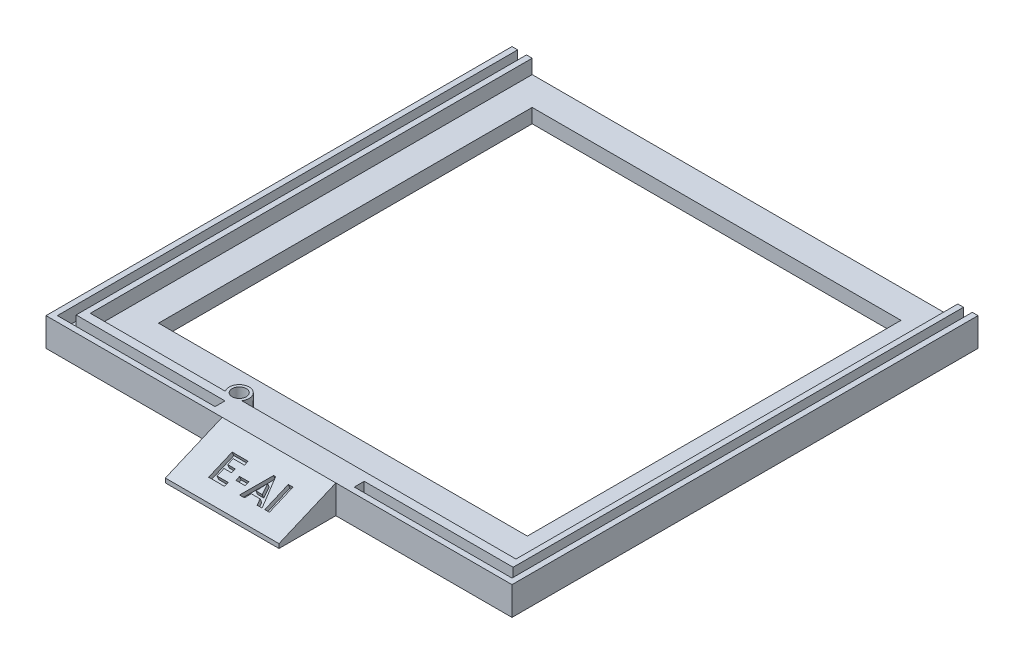
SolidWorks part; units mm, degrees
ref_plane "Front Plane" through (0, 0, 0) normal (0, 0, 1) x (1, 0, 0)
ref_plane "Top Plane" through (0, 0, 0) normal (0, 1, 0) x (1, 0, 0)
ref_plane "Right Plane" through (0, 0, 0) normal (1, 0, 0) x (0, 0, -1)
sketch "Sketch1" plane through (0, 0, 0) normal (0, 1, 0) x (1, 0, 0)
  line L1 (-82, 82) -> (82, 82)
  line L2 (-82, 82) -> (-82, -82)
  line L3 (-82, -82) -> (82, -82)
  line L4 (82, 82) -> (82, -82)
  line L5 (-82, 82) -> (82, -82) construction
  line L6 (-82, -82) -> (82, 82) construction
  point P0 (0, 0)
  dimension "D1" = 164
  dimension "D2" = 164
extrude "Boss-Extrude1" add sketch "Sketch1" along normal blind 5
sketch "Sketch2" plane through (0, 5, 0) normal (0, 1, 0) x (1, 0, 0)
  line L0 (-80, 80) -> (-80, 82)
  line L1 (-82, 82) -> (82, 82)
  line L2 (-82, 82) -> (-82, -82)
  line L3 (-82, -82) -> (-24.5, -82)
  line L4 (82, 82) -> (82, -82)
  line L5 (-82, 82) -> (82, -82) construction
  line L6 (-82, -82) -> (82, 82) construction
  line L8 (-80, 80) -> (-80, -80)
  line L9 (-80, -80) -> (-24.5, -80)
  line L10 (80, 80) -> (80, -80)
  line L11 (-80, 80) -> (80, -80) construction
  line L12 (-80, -80) -> (80, 80) construction
  line L13 (80, 80) -> (80, 82)
  line L14 (-24.5, -78.25) -> (24.5, -78.25) construction
  line L15 (-76.9, 82) -> (-76.9, -76.5)
  line L16 (-76.9, -76.5) -> (-24.5, -76.5)
  line L17 (76.9, -76.5) -> (76.9, 82)
  line L18 (-74.9, 82) -> (-74.9, -74.5)
  line L19 (-74.9, -74.5) -> (74.9, -74.5)
  line L20 (74.9, -74.5) -> (74.9, 82)
  line L21 (-24.5, -82) -> (24.5, -82)
  line L23 (-24.5, -82) -> (-24.5, -74.5)
  line L24 (24.5, -82) -> (24.5, -74.5)
  line L25 (0, -78.25) -> (0, -74.5) construction
  line L26 (24.5, -82) -> (82, -82)
  line L27 (24.5, -80) -> (80, -80)
  line L28 (-82, 82) -> (82, 82)
  line L29 (24.5, -76.5) -> (76.9, -76.5)
  point P0 (0, 0)
  point P7 (0, 0)
  line M17 (82, -82) -> (82, 82)
  line M18 (82, 82) -> (-82, 82)
  line M19 (-82, 82) -> (-82, -82)
  line M20 (-82, -82) -> (82, -82)
  dimension "D1" = 2
  dimension "D2" = 2
  dimension "D3" = 3.1
  dimension "D4" = 3.1
  dimension "D5" = 3.5
  dimension "D6" = 2
  dimension "D7" = 2
  dimension "D8" = 2
  dimension "D11" = 49
  dimension "D12" = 2
extrude "Boss-Extrude2" add sketch "Sketch2" along normal blind 5 contours L23 L9 L8 L0 M20 M18 M19 | L16 L23 L19 L18 L1 L15 | L24 L29 L17 L20 L19 M18 | L27 L24 L13 L10 M20 M17 M18 | L24 L19 M20 | L23 L3 L19 region at (-81.7379, 5, 0) region at (-75.9, 5, -80.3306) region at (0, 5, 78.25) region at (75.9, 5, -80.3306) region at (26.2379, 5, 81)
sketch "Sketch3" plane through (0, 5, 0) normal (0, 1, 0) x (1, 0, 0)
  line L0 (-24.5, -71.5) -> (-24.5, -76.5) construction
  circle A0 centre (-24.5, -71.5) radius 2.5
  circle A1 centre (-24.5, -71.5) radius 3.5
  dimension "D1" = 5
  dimension "D3" = 7
  dimension "D4" = 5
extrude "Boss-Extrude3" add sketch "Sketch3" along normal blind 5
sketch "Sketch5" plane through (0, 5, 0) normal (0, 1, 0) x (1, 0, 0)
  line L0 (-64.9, 72) -> (64.9, 72)
  line L1 (64.9, 72) -> (64.9, -59.5)
  line L2 (64.9, -59.5) -> (-64.9, -59.5)
  line L3 (-64.9, -59.5) -> (-64.9, 72)
  line L4 (-74.9, 82) -> (-74.9, -74.5) construction
  line L5 (74.9, -74.5) -> (74.9, 82) construction
  line L6 (74.9, 82) -> (-74.9, 82) construction
  line L7 (-74.9, -74.5) -> (-26.3028, -74.5) construction
  dimension "D1" = 10
  dimension "D2" = 10
  dimension "D3" = 10
  dimension "D4" = 15
extrude "Cut-Extrude1" cut sketch "Sketch5" against normal through all
chamfer "Chamfer2" distance 6 angle 45 2 edges at (-50.6014, 5, 74.5) (26.1014, 5, 74.5)
sketch "Sketch6" plane through (0, 0, 0) normal (1, 0, 0) x (0, 0, -1)
  line L4 (-82, 0) -> (-82, 10)
  line L6 (-102, 0) -> (-82, 0)
  line L7 (-82, 10) -> (-102, 1.5)
  line L8 (-102, 1.5) -> (-102, 0)
  dimension "D1" = 20
  dimension "D2" = 1.5
extrude "Boss-Extrude4" add sketch "Sketch6" along normal mid plane 40
sketch "Sketch7" plane through (0, -16.9382, 145.384) normal (0, -0.9203, -0.3911) x (1, 0, 0)
  line L0 (-20, -53.1396) -> (20, -53.1396) construction
  line L4 (-20, -68.8709) -> (-20, -47.1396) construction
  line L5 (20, -68.8709) -> (20, -47.1396) construction
  line L6 (20, -47.1396) -> (-20, -47.1396) construction
  text T0 "<b>E-AI</b>" font "Trebuchet MS" height 9
  dimension "D1" = 6
extrude "Cut-Extrude3" cut sketch "Sketch7" along normal blind 1.5
